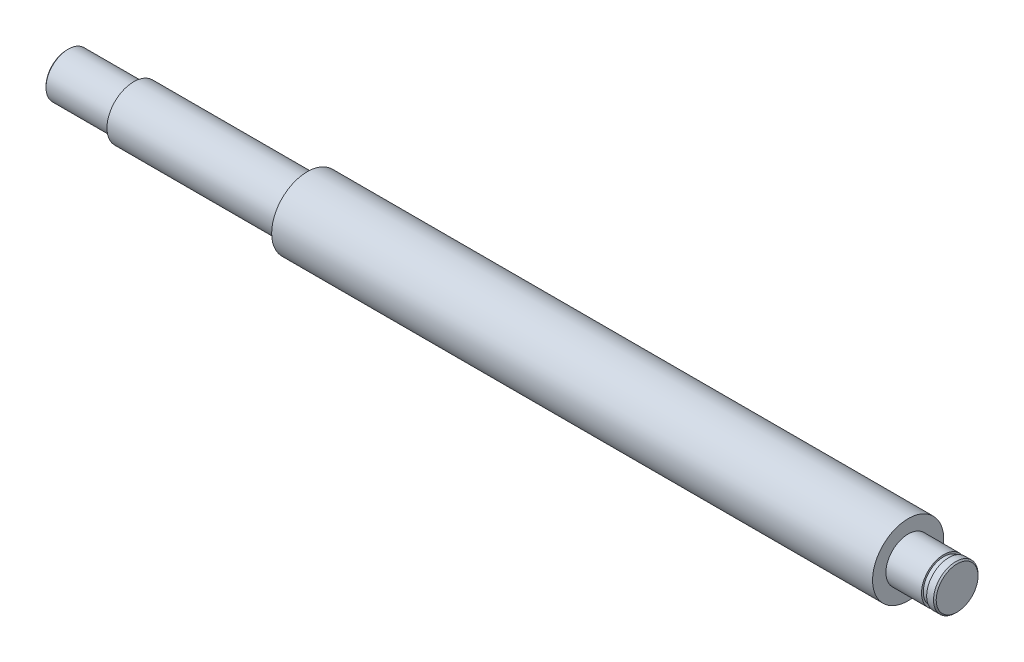
SolidWorks part; units mm, degrees
material "Легированная сталь"
ref_plane "Спереди" through (0, 0, 0) normal (0, 0, 1) x (1, 0, 0)
ref_plane "Сверху" through (0, 0, 0) normal (0, 1, 0) x (1, 0, 0)
ref_plane "Справа" through (0, 0, 0) normal (1, 0, 0) x (0, 0, -1)
sketch "Эскиз1" plane through (0, 0, 0) normal (0, 0, 1) x (1, 0, 0)
  line L0 (-100, 0) -> (100, 0)
  line L1 (-100, 0) -> (-100, 5)
  line L2 (-100, 5) -> (-85, 5)
  line L3 (-85, 5) -> (-85, 6)
  line L4 (-85, 6) -> (-46, 6)
  line L5 (-46, 6) -> (-46, 8)
  line L6 (-46, 8) -> (89, 8)
  line L7 (89, 8) -> (89, 5)
  line L8 (89, 5) -> (100, 5)
  line L9 (100, 5) -> (100, 0)
  dimension "D1" = 200
  dimension "D2" = 11
  dimension "D3" = 5
  dimension "D4" = 15
  dimension "D5" = 5
  dimension "D6" = 39
  dimension "D7" = 6
  dimension "D8" = 8
revolve "Повернуть1" add sketch "Эскиз1" angle 360 about L0
cosmetic thread "Условное изображение резьбы2" parameters "D1"=14, "D2"=10.072
sketch "Эскиз2" plane through (0, 0, 0) normal (0, 0, 1) x (1, 0, 0)
  line L0 (100, 5) -> (89, 5) construction
  line L1 (97, 5) -> (98.15, 5)
  line L2 (97, 5) -> (97, 4.6)
  line L3 (97, 4.6) -> (98.15, 4.6)
  line L4 (98.15, 5) -> (98.15, 4.6)
  line L5 (89, 0) -> (100, 0) construction
  line L6 (89, -8) -> (89, 8) construction
  line L7 (100, -5) -> (100, 5) construction
  dimension "D1" = 1.15
  dimension "D2" = 9.15
  dimension "D3" = 4.6
revolve "Вырез-Повернуть1" cut sketch "Эскиз2" angle 360 about L5
sketch "Эскиз3" plane through (-100, 0, 0) normal (-1, 0, 0) x (0, 0, 1)
  circle A0 centre (0, 0) radius 8
  dimension "D1" = 16
curve "Спираль1" pitch 5 height 250 turns 50
sketch "Эскиз4" plane through (0, 0, 0) normal (0, 0, 1) x (1, 0, 0)
  line L0 (-100, 5) -> (-100, -5) construction
  line L2 (-97.6, 7.8) -> (-97.4, 7.8)
  line L3 (-97.6, 7.8) -> (-97.6, 8.4)
  line L4 (-97.6, 8.4) -> (-97.4, 8.4)
  line L5 (-97.4, 7.8) -> (-97.4, 8.4)
  circle A0 centre (-100, 8.4) radius 1.9
  point P2 (-100, 0)
  point P10 (-97.5, 7.8)
  dimension "D1" = 3.8
  dimension "D2" = 8.4
  dimension "D3" = 0.2
  dimension "D4" = 2.5
  dimension "D5" = 7.8
sweep "Вырез-По траектории1" [suppressed] cut profiles "Эскиз4" path "Спираль1"
fillet "Скругление1" [suppressed] radius 0.2
chamfer "Фаска1" distance 0.3 angle 45 2 edges at (-100, 0, 5) (100, 0, 5)
